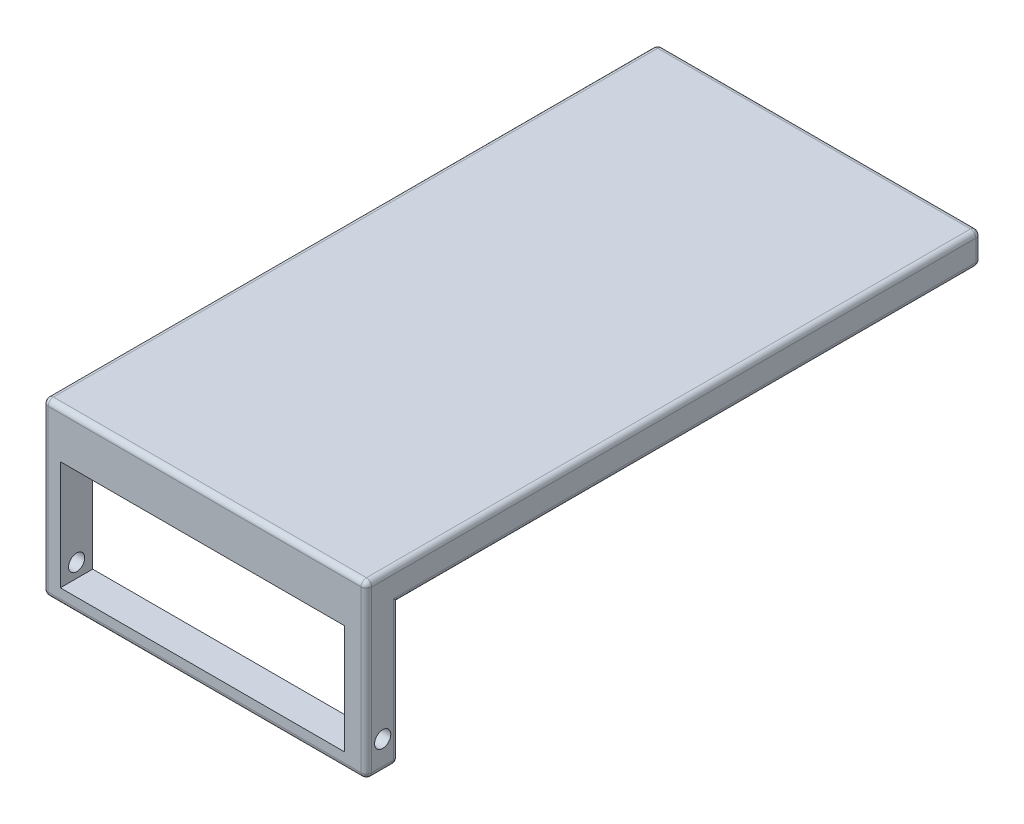
SolidWorks part; units mm, degrees
ref_plane "Front Plane" through (0, 0, 0) normal (0, 0, 1) x (1, 0, 0)
ref_plane "Top Plane" through (0, 0, 0) normal (0, 1, 0) x (1, 0, 0)
ref_plane "Right Plane" through (0, 0, 0) normal (1, 0, 0) x (0, 0, -1)
other "Center of Mass"
sketch "Sketch1" plane through (0, 0, 0) normal (1, 0, 0) x (0, 0, -1)
  line L0 (0, 375.5231) -> (0, -669.852) construction
  line L1 (-925.9292, 0) -> (1147.9054, 0) construction
  line L2 (-50.8, 122.0756) -> (914.4, 122.0756)
  line L3 (914.4, 122.0756) -> (914.4, 72.2916)
  line L4 (914.4, 72.2916) -> (0, 72.2916)
  line L5 (0, 72.2916) -> (0, -147.1644)
  line L6 (0, -147.1644) -> (-50.8, -147.1644)
  line L7 (-50.8, -147.1644) -> (-50.8, 122.0756)
  circle A0 centre (-25.2201, -101.7245) radius 12.7
  point P7 (0, 0)
  point P14 (-25.2201, -101.7245)
  dimension "D5" = 25.4
  dimension "D1" = 965.2
  dimension "D2" = 269.24
  dimension "D3" = 49.784
  dimension "D4" = 50.8
extrude "Boss-Extrude1" add sketch "Sketch1" along normal mid plane 508
sketch "Sketch2" plane through (0, 72.2916, 0) normal (0, -1, 0) x (1, 0, 0)
  line L0 (0, -133.2604) -> (0, -662.7245) construction
  line L1 (-254, 0) -> (-254, -914.4) construction
  line L6 (254, -914.4) -> (-254, -914.4) construction
  circle A8 centre (-127, -787.4) radius 6.35
  circle A9 centre (127, -787.4) radius 6.35
  point P9 (0, 0)
  dimension "D1" = 12.7
  dimension "D2" = 127
  dimension "D3" = 127
fillet "Fillet1" radius 8.382 12 edges at (0, 122.0756, -914.4) (254, 122.0756, -431.8) (0, 122.0756, 50.8) (-254, 122.0756, -431.8) (-254, 97.1836, -914.4) (254, 97.1836, -914.4) (0, 72.2916, -914.4) (254, 72.2916, -457.2) (254, -37.4364, 0) (0, -147.1644, 50.8) (-254, -12.5444, 50.8) (254, -12.5444, 50.8)
fillet "Fillet2" radius 8.382 6 edges at (-251.545, -144.7094, 48.345) (251.545, -144.7094, 48.345) (-254, -147.1644, 21.209) (254, -147.1644, 25.4) (251.545, -147.1644, 2.455) (-4.191, -147.1644, 0)
sketch "Sketch6" plane through (0, 0, 50.8) normal (0, 0, 1) x (1, 0, 0)
  line L1 (-226.5606, 47.9319) -> (219.3396, 47.9319)
  line L2 (-226.5606, 47.9319) -> (-226.5606, -123.5682)
  line L3 (-226.5606, -123.5682) -> (219.3396, -123.5682)
  line L4 (219.3396, 47.9319) -> (219.3396, -123.5682)
extrude "Cut-Extrude4" cut sketch "Sketch6" against normal through all
extrude "Cut-Extrude5" cut sketch "Sketch2" against normal blind 38.1
